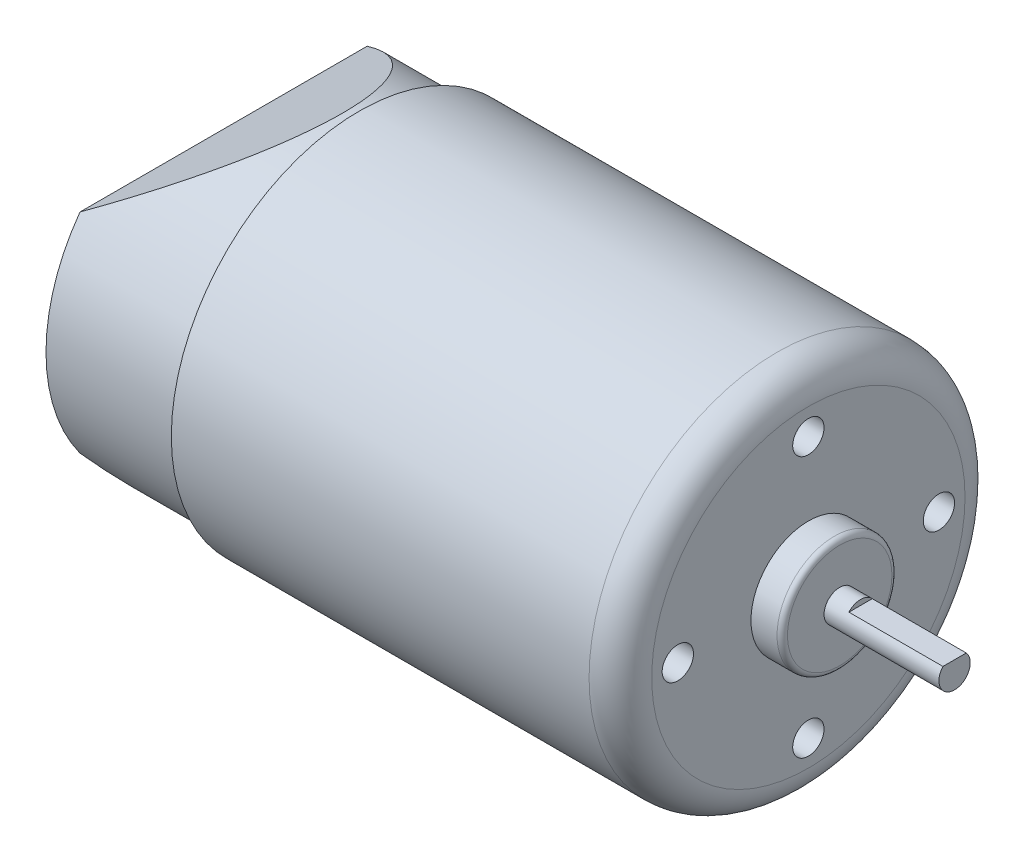
SolidWorks part; units mm, degrees
ref_plane "Front Plane" through (0, 0, 0) normal (0, 0, 1) x (1, 0, 0)
ref_plane "Top Plane" through (0, 0, 0) normal (0, 1, 0) x (1, 0, 0)
ref_plane "Right Plane" through (0, 0, 0) normal (1, 0, 0) x (0, 0, -1)
sketch "Sketch1" plane through (0, 0, 0) normal (1, 0, 0) x (0, 0, -1)
  circle A0 centre (0, 0) radius 18
  dimension "D1" = 36
extrude "Boss-Extrude1" add sketch "Sketch1" along normal blind 56
fillet "Fillet1" radius 3 1 edges at (56, 0, -18)
sketch "Sketch2" plane through (0, 0, 0) normal (0, 0, 1) x (1, 0, 0)
  line L0 (13, 18) -> (0, 10)
  line L1 (53, 18) -> (0, 18) construction
  line L2 (0, 18) -> (0, -18) construction
  line L3 (0, 10) -> (0, -10)
  line L4 (0, -10) -> (13, -18)
  line L5 (0, -18) -> (53, -18) construction
  line L6 (13, -18) -> (0, -18)
  line L7 (0, -18) -> (-7.8038, 17.2258)
  line L8 (-7.8038, 17.2258) -> (0, 18)
  line L9 (0, 18) -> (13, 18)
  dimension "D1" = 13
  dimension "D2" = 8
extrude "Cut-Extrude1" cut sketch "Sketch2" against normal up to surface and the other way up to surface up to face at (53, 0, -18) other way up to face at (53, 0, -18)
sketch "Sketch3" plane through (0, 0, 0) normal (0, 0, 1) x (1, 0, 0)
  line L0 (13, 18) -> (13, 17)
  line L1 (13, 17) -> (0, 17)
  line L2 (0, 17) -> (0, 18)
  line L3 (-7.8038, 17.2258) -> (0, 18) construction
  line L4 (0, 18) -> (13, 18)
  line L6 (0, 10) -> (0, -10) construction
  line L7 (-1000, 0) -> (49000, 0) construction
  dimension "D1" = 1
revolve "Cut-Revolve1" cut sketch "Sketch3" angle 360 about L7
sketch "Sketch4" plane through (56, 0, 0) normal (1, 0, 0) x (0, 0, -1)
  circle A0 centre (0, 0) radius 5.5
  dimension "D1" = 11
extrude "Boss-Extrude2" add sketch "Sketch4" along normal blind 3
fillet "Fillet2" radius 0.5 1 edges at (59, 0, -5.5)
sketch "Sketch5" plane through (59, 0, 0) normal (1, 0, 0) x (0, 0, -1)
  circle A0 centre (0, 0) radius 1.5
  dimension "D1" = 3
extrude "Boss-Extrude3" add sketch "Sketch5" along normal blind 11
sketch "Sketch6" plane through (0, 0, 0) normal (0, 0, 1) x (1, 0, 0)
  line L0 (70, 1.5) -> (70, 1)
  line L1 (70, -1.5) -> (70, 1.5) construction
  line L2 (70, 1) -> (61, 1)
  line L3 (61, 1) -> (61, 1.5)
  line L4 (70, 1.5) -> (59, 1.5) construction
  line L5 (61, 1.5) -> (70, 1.5)
  dimension "D1" = 9
  dimension "D2" = 0.5
extrude "Cut-Extrude2" cut sketch "Sketch6" against normal up to surface and the other way up to surface up to face at (70, 0, -1.5) other way up to face at (70, 0, -1.5)
sketch "Sketch7" plane through (56, 0, 0) normal (1, 0, 0) x (0, 0, -1)
  circle A0 centre (0, 12.5) radius 1.5
  circle A1 centre (0, 0) radius 5.5 construction
  circle A2 centre (12.5, 0) radius 1.5
  circle A3 centre (0, -12.5) radius 1.5
  circle A4 centre (-12.5, 0) radius 1.5
  dimension "D1" = 3
  dimension "D2" = 12.5
  dimension "D3" = 4
extrude "Cut-Extrude3" cut sketch "Sketch7" against normal blind 3
